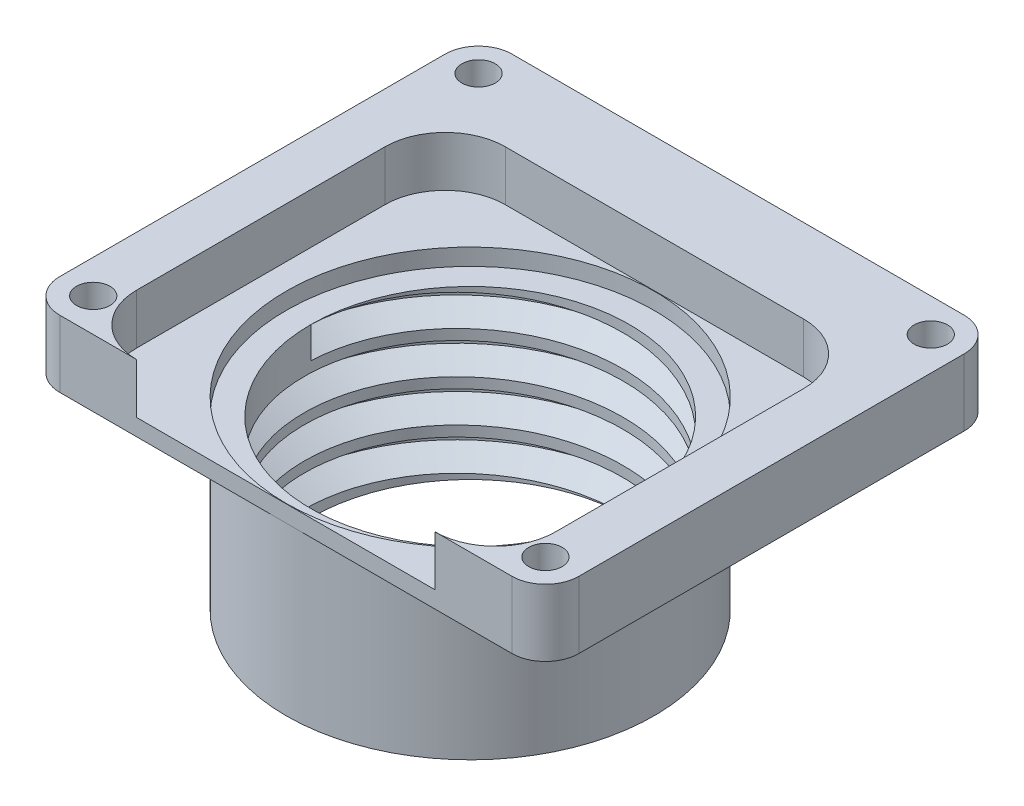
SolidWorks part; units mm, degrees
ref_plane "Front Plane" through (0, 0, 0) normal (0, 0, 1) x (1, 0, 0)
ref_plane "Top Plane" through (0, 0, 0) normal (0, 1, 0) x (1, 0, 0)
ref_plane "Right Plane" through (0, 0, 0) normal (1, 0, 0) x (0, 0, -1)
sketch "Sketch1" plane through (0, 0, 0) normal (0, 1, 0) x (1, 0, 0)
  line L0 (-17.1721, -17.1721) -> (17.1721, -17.1721)
  line L10 (19.7121, -14.6321) -> (19.7121, 14.6321)
  line L12 (-19.7121, -14.6321) -> (-19.7121, 14.6321)
  line L15 (17.1721, 17.1721) -> (-17.1721, 17.1721)
  line L16 (11.3301, 10.8221) -> (-11.3301, 10.8221)
  line L17 (-15.9021, -12.6001) -> (-15.9021, 6.2501)
  line L18 (-11.3301, -17.1721) -> (11.3301, -17.1721)
  line L19 (15.9021, -12.6001) -> (15.9021, 6.2501)
  line L20 (-15.9021, -3.175) -> (15.9021, -3.175)
  arc A0 (-19.7121, -14.6321) -> (-17.1721, -17.1721) centre (-17.1721, -14.6321) ccw
  arc A1 (17.1721, -17.1721) -> (19.7121, -14.6321) centre (17.1721, -14.6321) ccw
  arc A2 (19.7121, 14.6321) -> (17.1721, 17.1721) centre (17.1721, 14.6321) ccw
  arc A3 (-17.1721, 17.1721) -> (-19.7121, 14.6321) centre (-17.1721, 14.6321) ccw
  circle A4 centre (-17.1721, 14.6321) radius 1.27
  circle A9 centre (-17.1721, -14.6321) radius 1.27
  circle A10 centre (17.1721, 14.6321) radius 1.27
  circle A11 centre (17.1721, -14.6321) radius 1.27
  arc A18 (-11.3301, 10.8221) -> (-15.9021, 6.2501) centre (-11.3301, 6.2501) ccw
  arc A20 (15.9021, 6.2501) -> (11.3301, 10.8221) centre (11.3301, 6.2501) ccw
  circle A21 centre (0, -3.175) radius 13.97
  arc A22 (11.3301, -17.1721) -> (15.9021, -12.6001) centre (11.3301, -12.6001) ccw
  circle A23 centre (0, -3.175) radius 12.1044
  arc A24 (-11.3301, -17.1721) -> (-15.9021, -12.6001) centre (-11.3301, -12.6001) cw
  dimension "D1" = 2.54
  dimension "D3" = 4.572
  dimension "D4" = 4.572
  dimension "D5" = 4.572
  dimension "D6" = 4.572
extrude "Main Body" add sketch "Sketch1" along normal blind 5.08 contours L0 A24 L17 A18 L16 A20 L19 A22 A1 L10 A2 L15 A3 L12 A0 A11 A10 A9 A4 region at (-18.5984, 0, 16.0584)
extrude "Cover" add sketch "Sketch1<5>" along normal blind 1.27 contours A21 L20 L19 A20 L16 A18 L17 | A24 L0 A22 L19 L20 A21 L17 region at (-14.3173, 0, 15.5873) region at (-15.5546, 0, -1.5375)
sketch "Sketch1<5>" plane through (0, 0, 0) normal (0, 1, 0) x (1, 0, 0) same geometry as "Sketch1"
extrude "C-mount-joint" add sketch "Sketch1<6>" against normal blind 12.7 separate body contours A23 L20 A21 | A23 L20 A21 region at (0, 0, -10.4826) region at (-13.0372, 0, 3.4874)
sketch "Sketch1<6>" plane through (0, 0, 0) normal (0, 1, 0) x (1, 0, 0) same geometry as "Sketch1"
sketch "Sketch5" plane through (0, 1.27, 0) normal (0, 1, 0) x (1, 0, 0)
  circle A0 centre (0, -3.175) radius 13.208
extrude "Boss-Extrude1" [suppressed] add sketch "Sketch5" against normal up to surface (3.81 mm away)
thread "Thread1" pitch 3.175 method cut profile "Thread Profile1" start angle 0, offset 0, length 0, pitch 3.175, diameter 24.2087
ref_plane "Plane1" through (-12.1044, 0, 3.175) normal (0, 0, 1) x (-1, 0, 0)
sketch "Thread Profile1" plane through (-12.1044, 0, 3.175) normal (0, 0, 1) x (-1, 0, 0)
  line L0 (0, 0) -> (0, 3.175) construction
  line L1 (0, 0) -> (1.7185, 0.9922)
  line L2 (1.7185, 0.9922) -> (1.7185, 1.3891)
  line L3 (1.7185, 1.3891) -> (0, 2.3812)
  line L4 (1.7185, 1.1906) -> (0, 1.1906) construction
  line L11 (0, 0) -> (0, 2.3812)
  point P2 (0, 0)
  dimension "Pitch" = 3.175
  dimension "Profile_Angle" = 60
  dimension "Profile_Land" = 0.3969
  dimension "Profile_Height" = 1.7185
